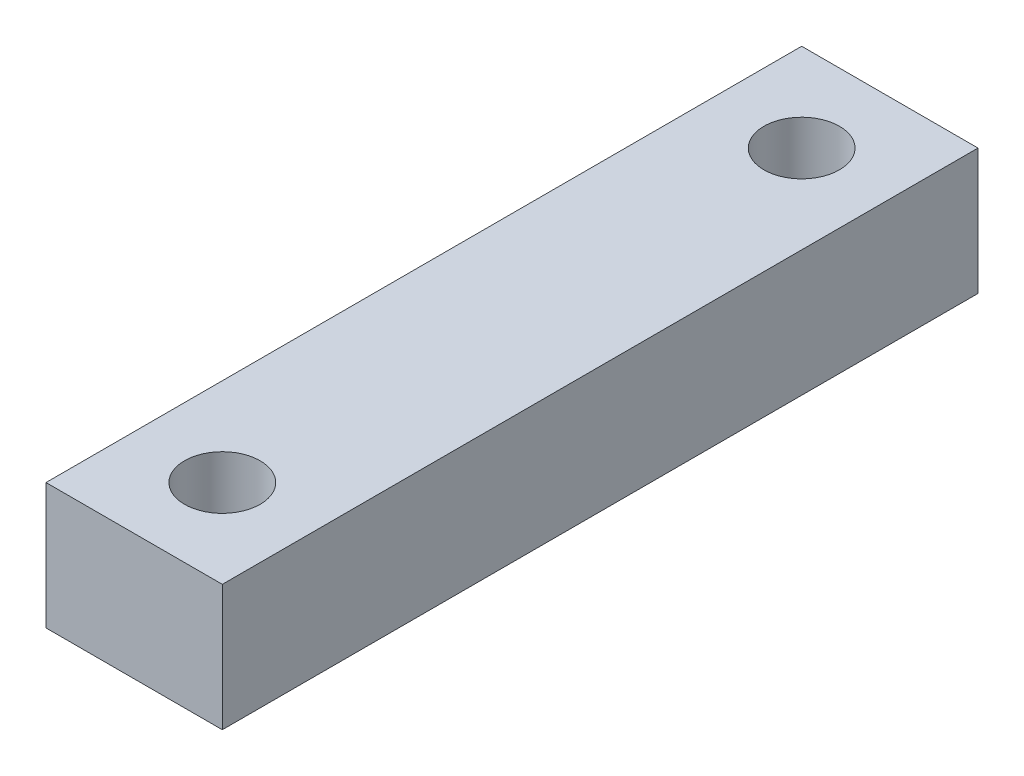
SolidWorks part; units mm, degrees
ref_plane "Piano frontale" through (0, 0, 0) normal (0, 0, 1) x (1, 0, 0)
ref_plane "Piano superiore" through (0, 0, 0) normal (0, 1, 0) x (1, 0, 0)
ref_plane "Piano destro" through (0, 0, 0) normal (1, 0, 0) x (0, 0, -1)
sketch "Schizzo1" plane through (0, 0, 0) normal (0, 0, 1) x (1, 0, 0)
  line L0 (0, 0) -> (-7, 0)
  line L1 (-7, 0) -> (-7, 5)
  line L2 (-7, 5) -> (0, 5)
  line L3 (0, 5) -> (0, 0)
  dimension "D1" = 7
  dimension "D2" = 5
extrude "Estrusione-Estrusione1" add sketch "Schizzo1" along normal blind 30
sketch "Schizzo2" plane through (0, 0, 0) normal (0, -1, 0) x (-1, 0, 0)
  line L0 (7, 0) -> (0, 0) construction
  line L1 (3.5, -30) -> (3.5, 3.3709) construction
  line L2 (7, -30) -> (0, -30) construction
  circle A0 centre (3.5, -26.5) radius 1.5
  circle A1 centre (3.5, -3.5) radius 1.5
  dimension "D3" = 3
  dimension "D1" = 3.5
  dimension "D2" = 3.5
extrude "Taglio-Estrusione1" cut sketch "Schizzo2" against normal through all
